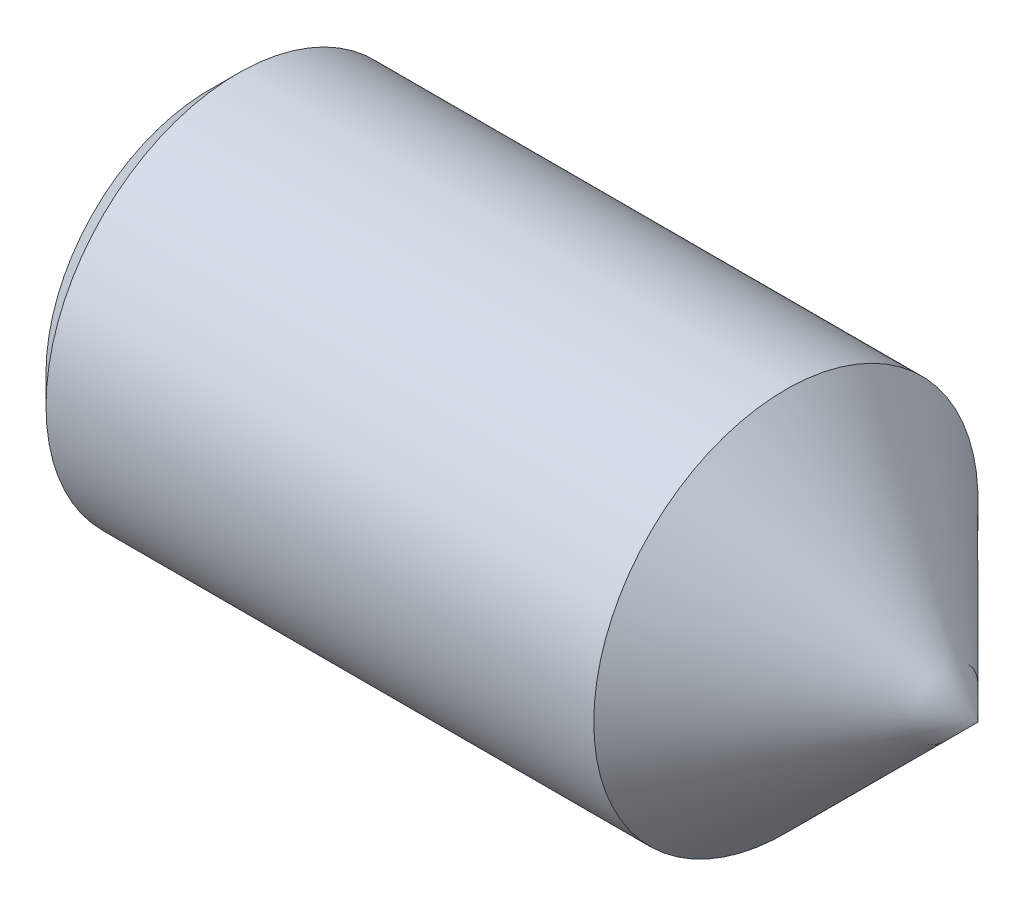
SolidWorks part; units mm, degrees
revolve "BaseBody" add sketch "BodySke" angle 360 about L5 other way angle 60
sketch "BodySke" plane through (0, 0, 0) normal (0, 0, 1) x (1, 0, 0)
  line L0 (0, 0) -> (0, 10.8102)
  line L1 (0, 10.8102) -> (1.8898, 12.7)
  line L2 (1.8898, 12.7) -> (38.1, 12.7)
  line L3 (38.1, 12.7) -> (50.8, 0)
  line L4 (50.8, 0) -> (0, 0)
  line L5 (-12.7, 0) -> (88.9, 0) construction
  line L6 (38.1, -12.7) -> (50.8, 0) construction
  line L7 (1.0541, 15.875) -> (1.0541, -3.175) construction
  line L8 (0, -10.8102) -> (1.8898, -12.7) construction
  dimension "Diameter" = 25.4
cosmetic thread "ThreadCosmetic" [suppressed] parameters "Thread_minor"=21.6205
ref_plane "Plane1" through (0, 0, 0) normal (0, 0, 1) x (1, 0, 0)
ref_plane "Plane2" through (0, 0, 0) normal (0, 1, 0) x (1, 0, 0)
ref_plane "Plane3" through (0, 0, 0) normal (1, 0, 0) x (0, 0, -1)
sketch "Sketch2" plane through (0, 0, 0) normal (-1, 0, 0) x (0, 0, 1)
  line L0 (4.1208, 7.1374) -> (-4.1208, 7.1374)
  line L1 (-4.1208, 7.1374) -> (-8.2416, 0)
  line L2 (4.1208, 7.1374) -> (8.2416, 0)
  line L3 (4.1208, -7.1374) -> (8.2416, 0)
  line L4 (4.1208, -7.1374) -> (-4.1208, -7.1374)
  line L5 (-4.1208, -7.1374) -> (-8.2416, 0)
  dimension "D2" = 7.1374
  dimension "D3" = 7.1374
extrude "Hex" cut sketch "Sketch2" against normal blind 14.2748
sketch "Sketch4" plane through (0, 4.7709, -0.5249) normal (-1, 0, 0) x (0, 0, 1)
  line L0 (0.5249, -4.7709) -> (10.6976, -4.7709)
  line L1 (0.5249, -4.7709) -> (6.6732, -1.2211) construction
  line L2 (0.5249, -4.7709) -> (5.6112, 4.0389)
  line L3 (8.9666, -2.6687) -> (10.2861, -1.9069)
  line L4 (6.5663, 1.4888) -> (7.8858, 2.2506)
  arc A0 (8.9666, -2.6687) -> (6.5663, 1.4888) centre (0.5249, -4.7709) ccw
  arc A1 (10.6976, -4.7709) -> (10.2861, -1.9069) centre (0.5249, -4.7709) ccw
  arc A2 (5.6112, 4.0389) -> (7.8858, 2.2506) centre (0.5249, -4.7709) cw
  circle A3 centre (0.5249, -4.7709) radius 8.6995 construction
  circle A4 centre (0.5249, -4.7709) radius 10.1727 construction
  dimension "Spline_n_dim" = 17.399
  dimension "Spline_m_dim" = 20.3454
  dimension "D1" = 30
  dimension "Spline_p_dim" = 4.8006
  dimension "D3" = 2.4003
extrude "Spline" [suppressed] cut sketch "Sketch4" against normal blind 12.7
pattern_circular "CirPattern1" [suppressed] count 6 every 60 about axis through (-12.7, 0, 0) along (1, 0, 0)
sketch "ThdSchSke" plane through (0, 0, 0) normal (0, 0, 1) x (1, 0, 0)
  line L0 (1.8898, -10.8102) -> (0.5665, -12.7)
  line L1 (1.8898, -10.8102) -> (3.213, -12.7)
  line L2 (3.213, -12.7) -> (3.213, -15.875)
  line L3 (-3.175, 0) -> (5.1513, 0) construction
  line L4 (1.8898, 12.7) -> (1.8898, -12.7) construction
  line L5 (3.213, -15.875) -> (0.5665, -15.875)
  line L6 (0.5665, -15.875) -> (0.5665, -12.7)
  dimension "Thread_minor" = 21.6205
  dimension "Diameter" = 25.4
revolve "ThreadSchematic" [suppressed] cut sketch "ThdSchSke" angle 360 about L3
pattern_linear "ThdSchPat" [suppressed]
equation "\"D2@Sketch2\" = \"Hex_size@Sketch2\" / 2"
equation "\"D3@Sketch2\" = \"Hex_size@Sketch2\" / 2"
equation "\"Thread_minor@ThreadCosmetic\" = \"Minor_dia@BodySke\""
equation "\"D1@Sketch4\" = \"Spline_a_dim@Sketch4\" / 2"
equation "\"D3@Sketch4\" = \"Spline_p_dim@Sketch4\" / 2"
equation "\"D2@CirPattern1\" = \"Spline_a_dim@Sketch4\""
equation "\"Num_teeth@CirPattern1\" = 360 / \"D2@CirPattern1\""
equation "\"Thread_minor@ThdSchSke\" = \"Thread_minor@ThreadCosmetic\""
equation "\"Diameter@ThdSchSke\" = \"Diameter@BodySke\""
equation "\"Overcut@ThdSchSke\" = \"Diameter@BodySke\" * 1.25"
equation "\"Num_threads@ThdSchPat\" = int( (\"Length@BodySke\" - ( ( ( \"Diameter@BodySke\" - \"Minor_dia@BodySke\" ) * 0.5 ) / tan( \"Drive_ch_ang@BodySke\" * 0.017453292 ) ) - ( ( \"Diameter@BodySke\" * 0.5 ) / tan( \"Cone_ang@BodySke\" * 0.008726646 ) ) ) / \"Advance@BodySke\" + 0.999 )  + 1"
equation "\"Advance@ThdSchPat\" = (\"Length@BodySke\" - ( ( ( \"Diameter@BodySke\" - \"Minor_dia@BodySke\" ) * 0.5 ) / tan( \"Drive_ch_ang@BodySke\" * 0.017453292 ) ) - ( ( \"Diameter@BodySke\" * 0.5 ) / tan( \"Cone_ang@BodySke\" * 0.008726646 ) ) ) /  (\"Num_threads@ThdSchPat\" - 1) 'relax it"
equation "' \"Num_threads@ThdSchPat\" = \"Num_threads@ThdSchPat\" - sgn( \"Num_threads@ThdSchPat\" - 1) '---chamfered tips only---"
